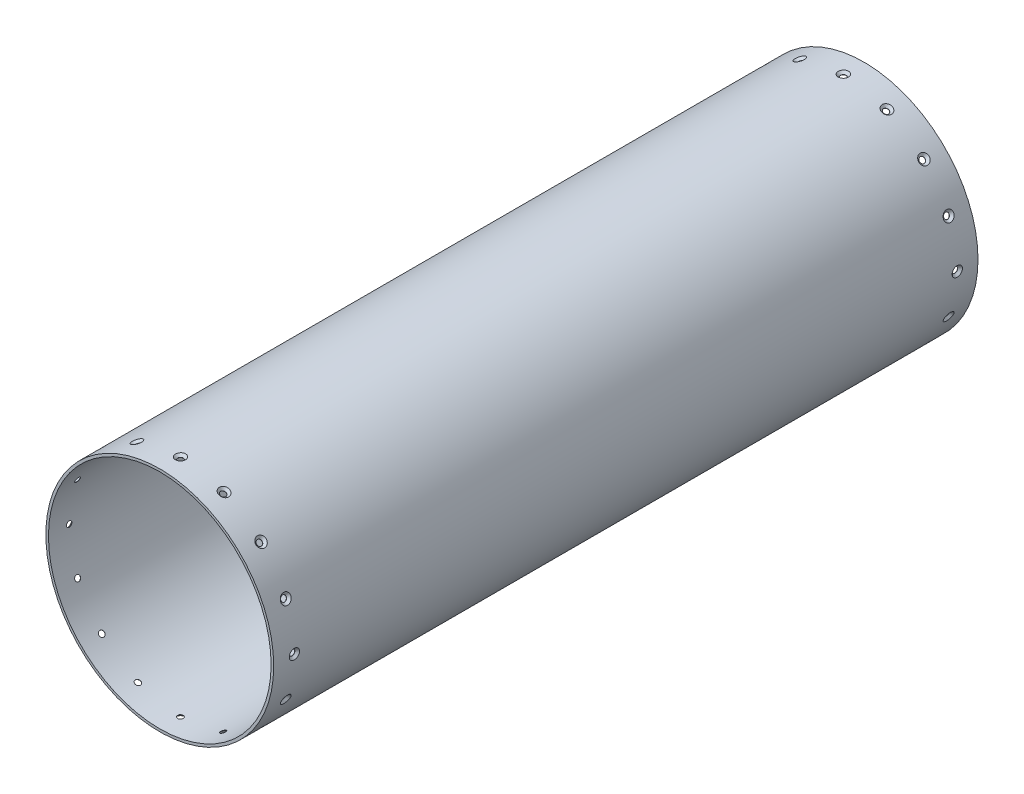
SolidWorks part; units mm, degrees
material "6061-T6 (SS)"
ref_plane "Front Plane" through (0, 0, 0) normal (0, 0, 1) x (1, 0, 0)
ref_plane "Top Plane" through (0, 0, 0) normal (0, 1, 0) x (1, 0, 0)
ref_plane "Right Plane" through (0, 0, 0) normal (1, 0, 0) x (0, 0, -1)
sketch "Sketch1" plane through (0, 0, 0) normal (0, 0, 1) x (1, 0, 0)
  circle A0 centre (0, 0) radius 69.85
  circle A1 centre (0, 0) radius 68.2625
  dimension "D1" = 139.7
  dimension "D2" = 1.5875
extrude "Extrude1" add sketch "Sketch1" along normal blind 431.8
ref_plane "Plane1" through (0, 0, 12.7) normal (0, 0, -1) x (-1, 0, 0)
sketch "Sketch2" plane through (0, 0, 12.7) normal (0, 0, -1) x (-1, 0, 0)
  line L0 (0, 0) -> (0, -69.85) construction
  circle A0 centre (0, 0) radius 69.85 construction
ref_plane "Plane2" through (0, -69.85, 12.7) normal (0, -1, 0) x (1, 0, 0)
hole_wizard "CSK for M3 Flat Head Machine Screw1" positions "Sketch5" profile "Sketch4" countersink size "M3" standard "Ansi Metric" end condition through all
sketch "Sketch5" plane through (0, -69.85, 12.7) normal (0, -1, 0) x (1, 0, 0)
  point P2 (0, 0)
sketch "Sketch4" plane through (0, -69.85, 12.7) normal (1, 0, 0) x (0, 0, -1)
  line L0 (0, 0) -> (0, 161.1134)
  line L1 (0, 161.1134) -> (1.7, 161.1134)
  line L2 (1.7, 161.1134) -> (1.7, 1.45)
  line L3 (1.7, 1.45) -> (3.15, 0)
  line L5 (3.15, 0) -> (0, 0)
  line L6 (-1.7, 1.45) -> (-3.15, 0) construction
  line L11 (0, -6.35) -> (0, 107.95) construction
  dimension "Thru Hole Dia." = 3.4
  dimension "Thru Hole Depth" = 161.1134
  dimension "Near C'Sink Dia." = 6.3
  dimension "Near C'Sink Angle" = 90
pattern_circular "CirPattern1" count 16 over 360 about axis through (0, 0, 431.8) along (0, 0, -1) of "CSK for M3 Flat Head Machine Screw1"
ref_plane "Plane3" through (0, 0, 420.6875) normal (0, 0, 1) x (1, 0, 0)
ref_plane "Plane5" through (0, 0, 0) normal (0.8315, 0.5556, 0) x (-0.5556, 0.8315, 0)
ref_plane "Plane7" through (0, 0, 0) normal (0.5556, -0.8315, 0) x (0.8315, 0.5556, 0)
ref_plane "Plane9" through (0, 0, 0) normal (-0.1951, -0.9808, 0) x (0.9808, -0.1951, 0)
sketch "Sketch7" plane through (0, 0, 431.8) normal (0, 0, 1) x (1, 0, 0)
  circle A0 centre (0, 0) radius 69.85 construction
  point P0 (69.85, 0)
ref_plane "Plane8" through (-68.5079, 13.6271, 215.9) normal (-0.9808, 0.1951, 0) x (0.1951, 0.9808, 0)
sketch "Sketch8" plane through (-68.5079, 13.6271, 215.9) normal (-0.9808, 0.1951, 0) x (0.1951, 0.9808, 0)
  line L0 (0, -425.45) -> (0, -414.3248) construction
pattern_linear "LPattern1" count 2 spacing 406.4 along (0, 0, 1) of "CirPattern1"
